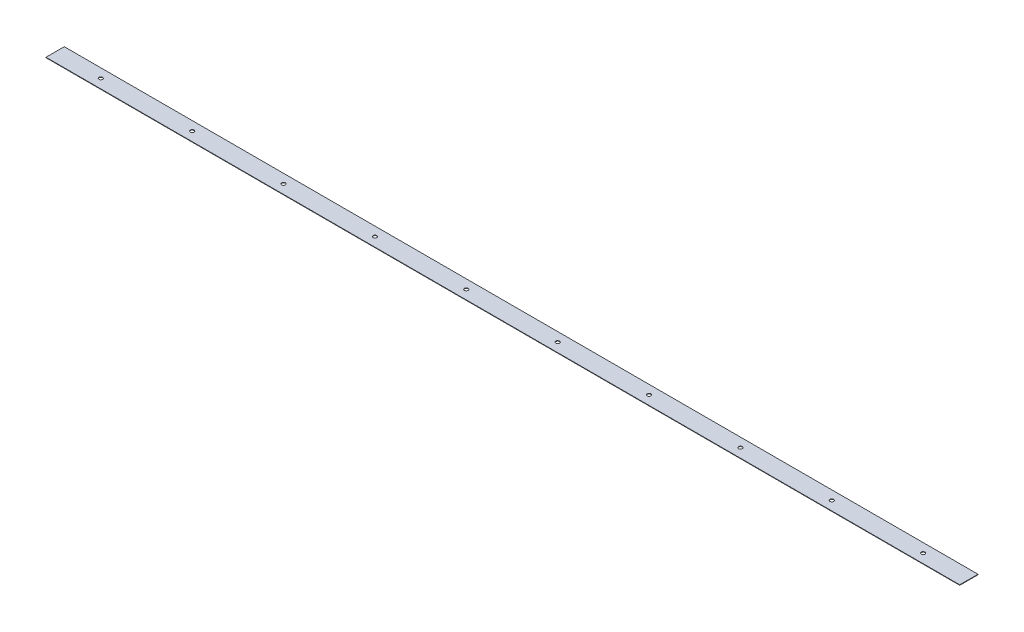
SolidWorks part; units mm, degrees
material "Galvanized Steel"
ref_plane "Front Plane" through (0, 0, 0) normal (0, 0, 1) x (1, 0, 0)
ref_plane "Top Plane" through (0, 0, 0) normal (0, 1, 0) x (1, 0, 0)
ref_plane "Right Plane" through (0, 0, 0) normal (1, 0, 0) x (0, 0, -1)
sketch "Sketch1" plane through (0, 0, 0) normal (0, 1, 0) x (1, 0, 0)
  line L1 (-500, -10) -> (500, -10)
  line L2 (-500, -10) -> (-500, 10)
  line L3 (-500, 10) -> (500, 10)
  line L4 (500, -10) -> (500, 10)
  line L5 (-500, -10) -> (500, 10) construction
  line L6 (-500, 10) -> (500, -10) construction
  point P0 (0, 0)
base flange "Base-Flange1" sketch "Sketch1" thickness 0.5 reverse thickness direction no parameters "D1"=2
sketch "Sketch2" plane through (0, 0, 0) normal (0, 1, 0) x (1, 0, 0)
  circle A0 centre (-450, 0) radius 2
  circle A1 centre (-350, 0) radius 2
  circle A2 centre (-250, 0) radius 2
  circle A3 centre (-150, 0) radius 2
  circle A4 centre (-50, 0) radius 2
  circle A5 centre (50, 0) radius 2
  circle A6 centre (150, 0) radius 2
  circle A7 centre (250, 0) radius 2
  circle A8 centre (350, 0) radius 2
  circle A9 centre (450, 0) radius 2
extrude "Cut-Extrude1" cut sketch "Sketch2" against normal blind 10
sketch "Bend-Lines1" [suppressed] plane through (0, 0, 0) normal (0, 1, 0) x (1, 0, 0)
sketch "Bounding-Box1" [suppressed] plane through (0, 0, 0) normal (0, 1, 0) x (1, 0, 0)
sheet metal parameters "Sheet-Metal1" thickness 0.5 parameters "D1"=2
flat pattern "Flat-Pattern1" [suppressed]
sketch "Bend-Lines2" plane through (0, 0, 0) normal (0, 1, 0) x (1, 0, 0)
sketch3d "Bounding-Box2" [suppressed]
  line L0 (500, 10, 0) -> (-500, 10, 0) construction
  line L1 (500, -10, 0) -> (-500, -10, 0) construction
  line L2 (500, 10, 0) -> (500, -10, 0) construction
  line L3 (-500, 10, 0) -> (-500, -10, 0) construction
sheet metal parameters "Sheet-Metal3" thickness 0.5 parameters "D1"=2
flat pattern "Flat-Pattern1"
sketch "Bend-Lines2" plane through (0, 0, 0) normal (0, 1, 0) x (1, 0, 0)
sketch3d "Bounding-Box2" [suppressed]
  line L0 (500, 10, 0) -> (-500, 10, 0) construction
  line L1 (500, -10, 0) -> (-500, -10, 0) construction
  line L2 (500, 10, 0) -> (500, -10, 0) construction
  line L3 (-500, 10, 0) -> (-500, -10, 0) construction
